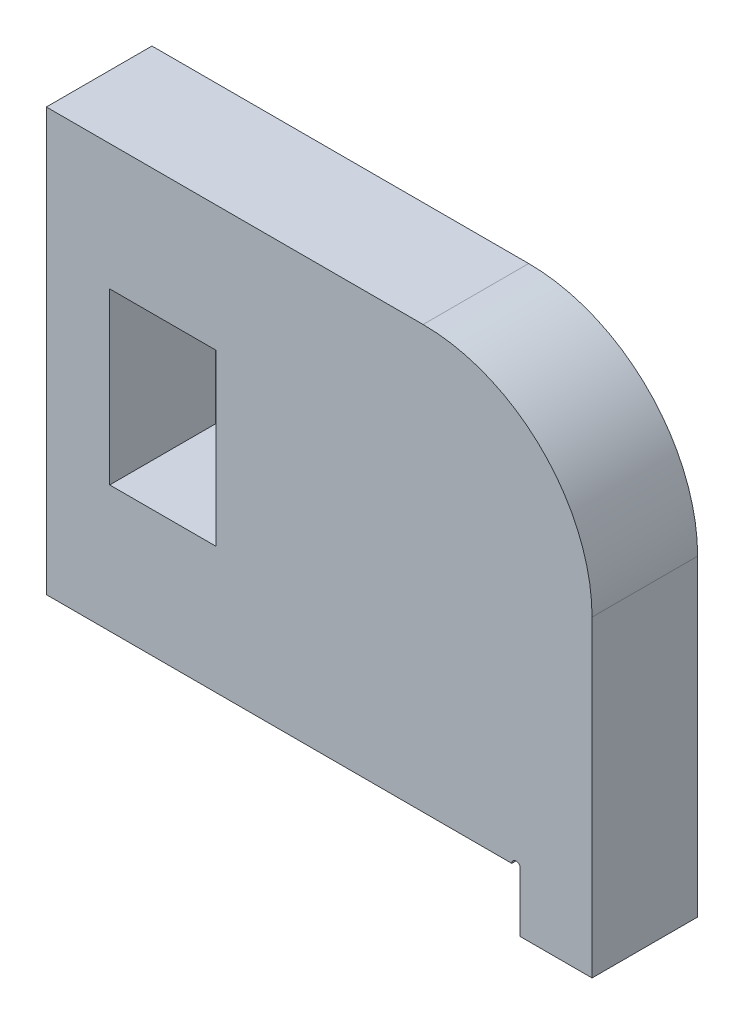
SolidWorks part; units mm, degrees
material "PBT General Purpose"
ref_plane "Front Plane" through (0, 0, 0) normal (0, 0, 1) x (1, 0, 0)
ref_plane "Top Plane" through (0, 0, 0) normal (0, 1, 0) x (1, 0, 0)
ref_plane "Right Plane" through (0, 0, 0) normal (1, 0, 0) x (0, 0, -1)
sketch "frame_outline" plane through (0, 0, 0) normal (0, 0, 1) x (1, 0, 0)
  line L110 (0, 0) -> (0, 1)
  line L121 (0.302, 0) -> (0, 0)
  line L122 (0, 1) -> (1.292, 1)
  line L123 (1.292, 1) -> (1.292, -0.14)
  line L124 (1.292, -0.14) -> (1.122, -0.14)
  line L125 (1.122, -0.14) -> (1.122, 0.01)
  line L126 (1.122, 0.01) -> (1.102, 0.01)
  line L127 (1.102, 0.01) -> (1.102, 0)
  line L128 (1.102, 0) -> (0.302, 0)
  line L131 (0.15, 0.702) -> (0.402, 0.702)
  line L132 (0.15, 0.702) -> (0.15, 0.3)
  line L133 (0.15, 0.3) -> (0.402, 0.3)
  line L134 (0.402, 0.702) -> (0.402, 0.3)
  dimension "D1" = 1
  dimension "D2" = 0.3
  dimension "D3" = 0.252
  dimension "D4" = 0.402
  dimension "D5" = 0.17
  dimension "D6" = 0.8
  dimension "D7" = 0.15
  dimension "D8" = 0.01
  dimension "D9" = 0.02
  dimension "D10" = 0.7
  dimension "D11" = 0.15
extrude "Boss-Extrude1" add sketch "frame_outline" along normal mid plane 0.25
fillet "Fillet1" radius 0.01 2 edges at (1.122, 0.01, 0) (1.102, 0.01, 0)
fillet "Fillet2" radius 0.4 1 edges at (1.292, 1, 0)
equation "\"t\"= 0.25'thickness of the sheets"
equation "\"t_cf\" = 0.115'thickness of single carbon fiber layer"
equation "\"t_kapton\" = 0.025'thickness of single Kapton flex layer"
equation "\"t_fr4\" = 0.1'thickness of FR4 with copper layer"
equation "\"joint_flex\"= 0.1'Width of flextures gap"
equation "\"joint_flex_eff\"= 0.02'Width of flecture after castelation"
equation "\"joint_fold\"= 0.2'Width of folding joints for 90deg fold"
equation "\"gap_tolerance\"= 0.002'Width to have interfecence fit between carbon fiber inserts"
equation "\"assemble_angle\"= 90'Angle of assembly parts"
equation "\"D1@Boss-Extrude1\"=\"t\""
equation "\"link_lift\"= 0.5'Actuation linkage amplification for the lift motion"
equation "\"link_swing\"= 0.45'Actuation linkage amplification for the swing motion"
equation "\"D3@frame_outline\"=\"t\"+\"gap_tolerance\""
equation "\"D4@frame_outline\"=0.4+\"gap_tolerance\""
equation "\"D5@frame_outline\"=0.17"
equation "\"D7@frame_outline\"=\"joint_fold\"-0.05"
